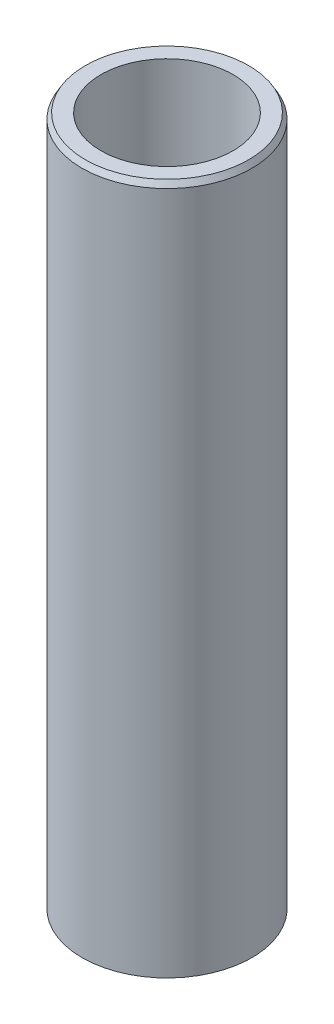
SolidWorks part; units mm, degrees
ref_plane "Front Plane" through (0, 0, 0) normal (0, 0, 1) x (1, 0, 0)
ref_plane "Top Plane" through (0, 0, 0) normal (0, 1, 0) x (1, 0, 0)
ref_plane "Right Plane" through (0, 0, 0) normal (1, 0, 0) x (0, 0, -1)
sketch "Sketch1" plane through (0, 0, 0) normal (0, 1, 0) x (1, 0, 0)
  circle A0 centre (0, 0) radius 52.5
  dimension "SHAFT_OD" = 105
extrude "Boss-Extrude1" add sketch "Sketch1" along normal blind 428.1144
sketch "Sketch2" plane through (0, 0, 0) normal (0, 1, 0) x (1, 0, 0)
  circle A0 centre (0, 0) radius 40.8383
  dimension "BORE_D" = 81.6766
extrude "Cut-Extrude1" cut sketch "Sketch2" along normal through all
chamfer "Chamfer1" distance 3.5358 angle 30 2 edges at (0, 428.1144, 52.5) (0, 0, 52.5) first distance on face at (0, 428.1144, 52.5) first distance on face at (0, 0, 40.8383)
